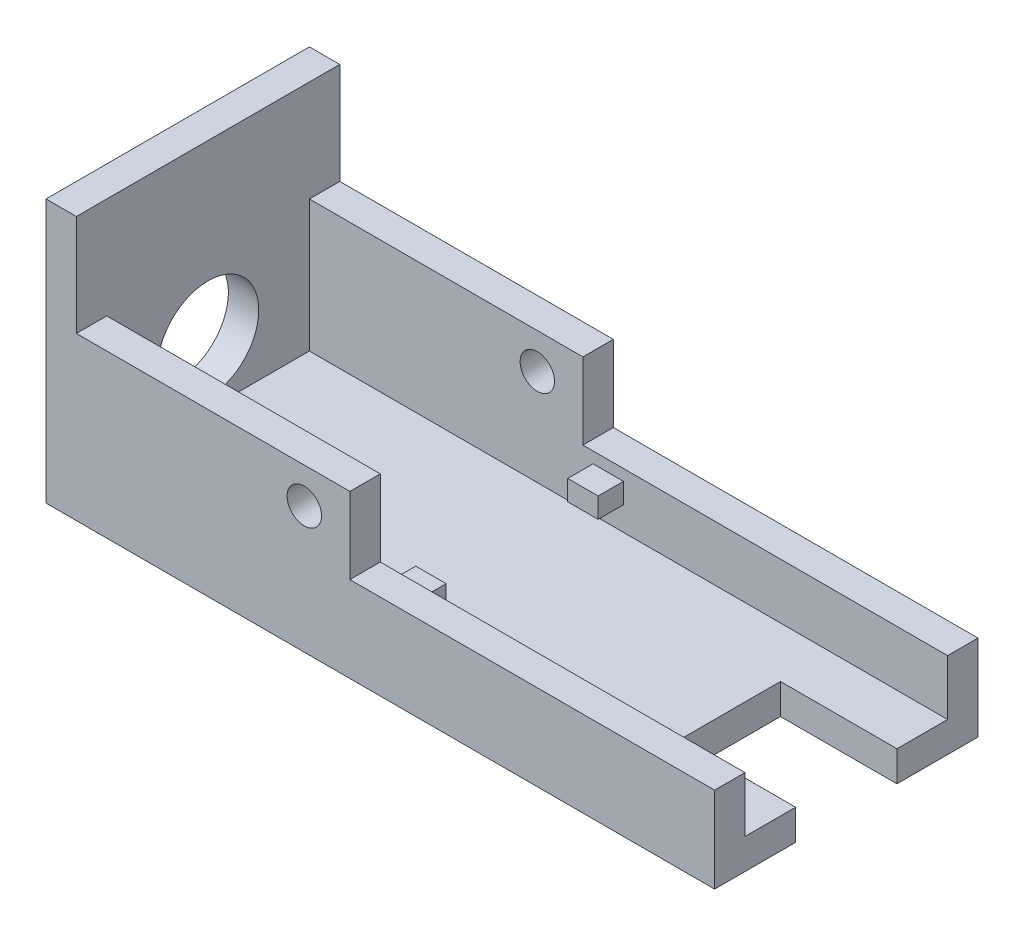
SolidWorks part; units mm, degrees
ref_plane "Front Plane" through (0, 0, 0) normal (0, 0, 1) x (1, 0, 0)
ref_plane "Top Plane" through (0, 0, 0) normal (0, 1, 0) x (1, 0, 0)
ref_plane "Right Plane" through (0, 0, 0) normal (1, 0, 0) x (0, 0, -1)
sketch "Sketch1" plane through (0, 0, 0) normal (0, 1, 0) x (1, 0, 0)
  line L0 (30, 10) -> (33, 10)
  line L1 (-30, -10) -> (30, -10)
  line L2 (-30, -10) -> (-30, 10)
  line L3 (-30, 10) -> (30, 10)
  line L4 (30, -10) -> (30, 10)
  line L5 (-30, -10) -> (30, 10) construction
  line L6 (-30, 10) -> (30, -10) construction
  line L7 (-33, -13) -> (33, -13)
  line L8 (-33, -13) -> (-33, 13)
  line L9 (-33, 13) -> (33, 13)
  line L10 (33, -13) -> (33, 13)
  line L11 (-33, -13) -> (33, 13) construction
  line L12 (-33, 13) -> (33, -13) construction
  line L13 (30, -10) -> (33, -10)
  point P0 (0, 0)
  point P6 (0, 0)
  dimension "D1" = 60
  dimension "D2" = 20
  dimension "D3" = 3
  dimension "D4" = 3
extrude "Boss-Extrude1" add sketch "Sketch1" along normal blind 3 contours L8 L9 L10 L7
extrude "Boss-Extrude2" add sketch "Sketch1<3>" along normal blind 3 from surface contours L13 L1 L2 L3 L0 L10 L9 L8 L7 region at (0, 0, -10.7094) starting at face at (0, 3, 0)
sketch "Sketch1<3>" plane through (0, 0, 0) normal (0, 1, 0) x (1, 0, 0) same geometry as "Sketch1"
sketch "Sketch2" plane through (0, 6, 0) normal (0, 1, 0) x (1, 0, 0)
  line L0 (-3, 13) -> (-3, 10)
  line L1 (-3, -10) -> (-3, -13)
  line L2 (-30, 10) -> (-30, 13)
  line L3 (-30, -10) -> (-30, -13)
  line L8 (33, -13) -> (33, -10)
  line L9 (33, -10) -> (-30, -10)
  line L10 (-30, -10) -> (-30, 10)
  line L11 (-30, 10) -> (33, 10)
  line L12 (33, 10) -> (33, 13)
  line L13 (33, 13) -> (-33, 13)
  line L14 (-33, 13) -> (-33, -13)
  line L15 (-33, -13) -> (33, -13)
  line L16 (33, -13) -> (33, -10)
  line L17 (33, -10) -> (-30, -10)
  line L18 (-30, -10) -> (-30, 10)
  line L19 (-30, 10) -> (33, 10)
  line L20 (33, 10) -> (33, 13)
  line L21 (33, 13) -> (-33, 13)
  line L22 (-33, 13) -> (-33, -13)
  line L23 (-33, -13) -> (33, -13)
  line M11 (33, -13) -> (33, -10)
  line M12 (33, -10) -> (-30, -10)
  line M13 (-30, -10) -> (-30, 10)
  line M14 (-30, 10) -> (33, 10)
  line M15 (33, 10) -> (33, 13)
  line M16 (33, 13) -> (-33, 13)
  line M17 (-33, 13) -> (-33, -13)
  line M18 (-33, -13) -> (33, -13)
  dimension "D2" = 27
  dimension "D1" = 0
extrude "Boss-Extrude3" add sketch "Sketch2" along normal blind 10 contours L1 L0 M12 M13 M14 M16 M17 M18 | L3 L1 M12 M18 | L2 L0 M14 M16 region at (-16.5, 6, -11.5) region at (-31.5, 6, 0) region at (-16.5, 6, 11.5)
extrude "Boss-Extrude4" add sketch "Sketch2<3>" along normal blind 10 from surface contours L3 L2 M13 M16 M17 M18 region at (-31.5, 6, 0) starting at face at (-17.25, 16, 0)
sketch "Sketch2<3>" plane through (0, 6, 0) normal (0, 1, 0) x (1, 0, 0) same geometry as "Sketch2"
extrude "Boss-Extrude5" add sketch "Sketch2<4>" along normal blind 2.46 contours L0 M16 M14 M15 | L1 M12 M18 M11 region at (15, 6, -11.5) region at (15, 6, 11.5)
sketch "Sketch2<4>" plane through (0, 6, 0) normal (0, 1, 0) x (1, 0, 0) same geometry as "Sketch2"
sketch "Sketch3" plane through (0, 0, -10) normal (0, 0, 1) x (1, 0, 0)
  line L0 (-3, 8.46) -> (33, 8.46) construction
  line L1 (-2, 7.36) -> (1, 7.36)
  line L2 (-2, 7.36) -> (-2, 5.36)
  line L3 (-2, 5.36) -> (1, 5.36)
  line L4 (1, 7.36) -> (1, 5.36)
  line L5 (-2, 7.36) -> (1, 5.36) construction
  line L6 (-2, 5.36) -> (1, 7.36) construction
  line L7 (-3, 16) -> (-3, 8.46) construction
  point P0 (-0.5, 6.36)
  dimension "D1" = 3
  dimension "D2" = 2
  dimension "D3" = 1.1
  dimension "D4" = 1
extrude "Boss-Extrude6" add sketch "Sketch3" along normal blind 2.5
mirror "Mirror1" about plane through (0, 0, 0) normal (0, 0, 1) of "Boss-Extrude6"
sketch "Sketch4" plane through (0, 0, 0) normal (0, -1, 0) x (1, 0, 0)
  line L0 (33, 13) -> (33, -13) construction
  line L1 (21.5, -5) -> (33, -5)
  line L2 (21.5, -5) -> (21.5, 5)
  line L3 (21.5, 5) -> (33, 5)
  line L4 (33, -5) -> (33, 5)
  line L5 (21.5, -5) -> (33, 5) construction
  line L6 (21.5, 5) -> (33, -5) construction
  point P0 (27.25, 0)
  point P7 (0, 0)
  dimension "D1" = 10
  dimension "D2" = 11.5
extrude "Cut-Extrude1" cut sketch "Sketch4" against normal through all both and the other way through all
sketch "Sketch5" plane through (0, 0, 13) normal (0, 0, 1) x (1, 0, 0)
  line L0 (-30, 16) -> (-3, 16) construction
  line L1 (-3, 16) -> (-3, 8.46) construction
  point P0 (-7.5, 12.5)
  dimension "D1" = 3.5
  dimension "D2" = 4.5
hole_wizard "M3 Clearance Hole1" positions "Sketch6" profile "Sketch7" hole size "M3" standard "ISO" end condition through all
sketch "Sketch6" plane through (0, 0, 13) normal (0, 0, 1) x (1, 0, 0)
  point P0 (-7.5, 12.5)
sketch "Sketch7" plane through (-7.5, 12.5, 13) normal (1, 0, 0) x (0, -1, 0)
  line L0 (0, 0) -> (0, 26)
  line L1 (0, 26) -> (1.7, 26)
  line L2 (1.7, 26) -> (1.7, 0)
  line L5 (1.7, 0) -> (0, 0)
  line L11 (0, -6.35) -> (0, 107.95) construction
  dimension "Thru Hole Dia." = 3.4
  dimension "Thru Hole Depth" = 26
sketch "Sketch8" plane through (-33, 0, 0) normal (-1, 0, 0) x (0, 0, 1)
  line L0 (13, 0) -> (-13, 0) construction
  circle A0 centre (0, 9) radius 5
  point P4 (0, 0)
  dimension "D1" = 10
  dimension "D2" = 9
extrude "Cut-Extrude2" cut sketch "Sketch8" against normal up to next
